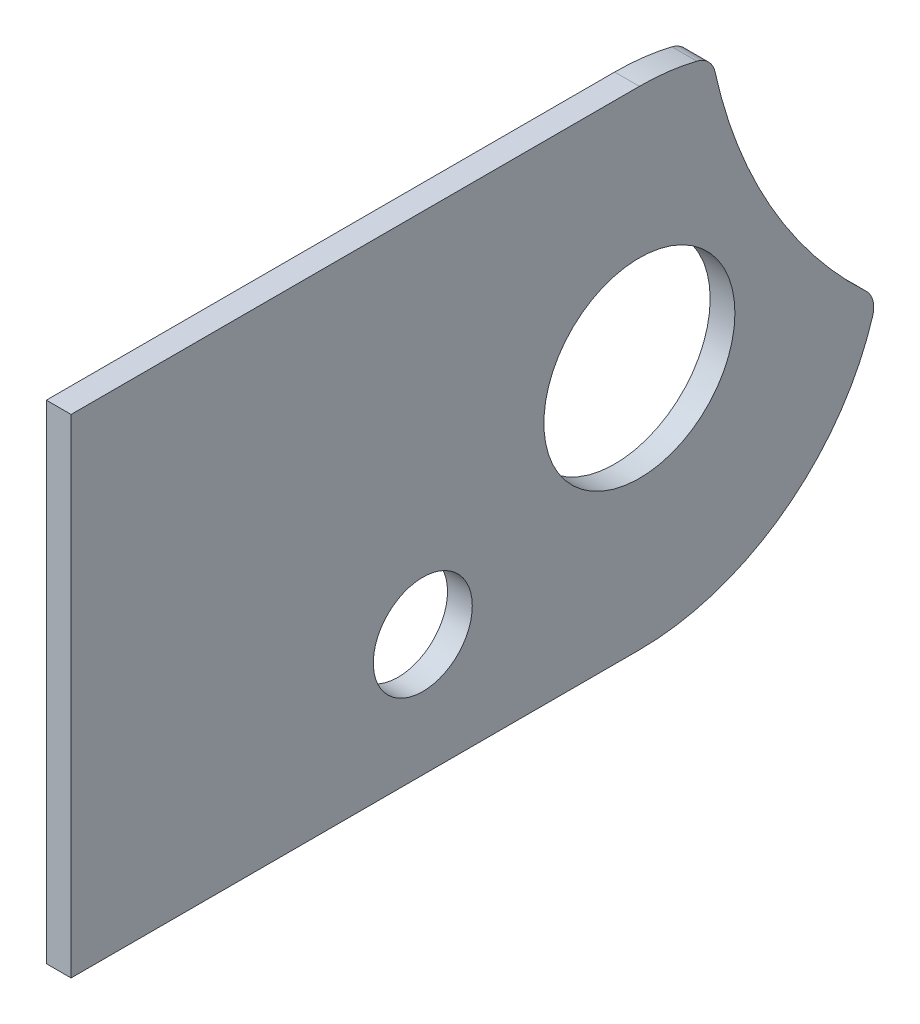
SolidWorks part; units mm, degrees
ref_plane "Front Plane" through (0, 0, 0) normal (0, 0, 1) x (1, 0, 0)
ref_plane "Top Plane" through (0, 0, 0) normal (0, 1, 0) x (1, 0, 0)
ref_plane "Right Plane" through (0, 0, 0) normal (1, 0, 0) x (0, 0, -1)
sketch "Sketch1" plane through (0, 0, 0) normal (1, 0, 0) x (0, 0, -1)
  line L0 (0, 24.65) -> (-57.407, 24.65)
  line L1 (-57.407, 24.65) -> (-57.407, -24.65)
  line L2 (-57.407, -24.65) -> (0, -24.65)
  circle A0 centre (0, 0) radius 9.65
  arc A2 (0, -24.65) -> (0, 24.65) centre (0, 0) ccw
  circle A3 centre (0, 0) radius 24.65 construction
  dimension "D1" = 19.3
  dimension "D3" = 57.407
  dimension "D2" = 15
base flange "Base-Flange1" sketch "Sketch1" thickness 2.5 reverse thickness direction no parameters "D1"=0.7366
sketch "Sketch2" plane through (0, 0, 0) normal (1, 0, 0) x (0, 0, -1)
  line L0 (0, -24.65) -> (-21.8798, -24.65) construction
  line L1 (-57.407, -24.65) -> (0, -24.65) construction
  line L2 (-21.8798, -24.65) -> (-21.8798, -12.3563) construction
  line L3 (0, 24.65) -> (0, 33.3401) construction
  line L4 (0, 33.3401) -> (58.593, 33.3401) construction
  circle A0 centre (-21.8798, -12.3563) radius 5
  circle A1 centre (58.593, 33.3401) radius 52.175
  dimension "D5" = 104.35
  dimension "D6" = 10
  dimension "D1" = 21.8798
  dimension "D2" = 12.2937
  dimension "D3" = 8.6901
  dimension "D4" = 58.593
extrude "Cut-Extrude1" cut sketch "Sketch2" against normal through all both and the other way through all normal cut yes
fillet "Fillet1" radius 2.5 2 edges at (-1.25, 23.5291, -7.3487) (-1.25, -5.7019, -23.9815)
scale "Scale1" scale about centroid uniform scaling yes scale factor 1.5
sketch "Bend-Lines1" [suppressed] plane through (0, 0, 0) normal (0, 1, 0) x (1, 0, 0)
sketch "Bounding-Box1" [suppressed] plane through (0, 0, 0) normal (0, 1, 0) x (1, 0, 0)
sheet metal parameters "Sheet-Metal1" thickness 2.5 parameters "D1"=0.7366
flat pattern "Flat-Pattern1" [suppressed]
sketch "Bend-Lines2" plane through (0, 0, 0) normal (0, 1, 0) x (1, 0, 0)
sketch3d "Bounding-Box2" [suppressed]
  line L0 (57.407, -24.65, 0) -> (-24.65, -24.65, 0) construction
  line L1 (57.407, 24.65, 0) -> (-24.65, 24.65, 0) construction
  line L2 (57.407, -24.65, 0) -> (57.407, 24.65, 0) construction
  line L3 (-24.65, -24.65, 0) -> (-24.65, 24.65, 0) construction
sheet metal parameters "Sheet-Metal2" thickness 2.5 parameters "D1"=0.7366
flat pattern "Flat-Pattern1"
sketch "Bend-Lines2" plane through (0, 0, 0) normal (0, 1, 0) x (1, 0, 0)
sketch3d "Bounding-Box2" [suppressed]
  line L0 (-57.407, -24.65, 0) -> (23.6684, -24.65, 0) construction
  line L1 (-57.407, 24.65, 0) -> (23.6684, 24.65, 0) construction
  line L2 (-57.407, -24.65, 0) -> (-57.407, 24.65, 0) construction
  line L3 (23.6684, -24.65, 0) -> (23.6684, 24.65, 0) construction
sheet metal parameters "Sheet-Metal3" thickness 2.5 parameters "D1"=0.7366
flat pattern "Flat-Pattern1"
sketch "Bend-Lines2" plane through (0, 0, 0) normal (0, 1, 0) x (1, 0, 0)
sketch3d "Bounding-Box2" [suppressed]
  line L0 (-57.407, -24.65, 0) -> (23.6684, -24.65, 0) construction
  line L1 (-57.407, 24.65, 0) -> (23.6684, 24.65, 0) construction
  line L2 (-57.407, -24.65, 0) -> (-57.407, 24.65, 0) construction
  line L3 (23.6684, -24.65, 0) -> (23.6684, 24.65, 0) construction
